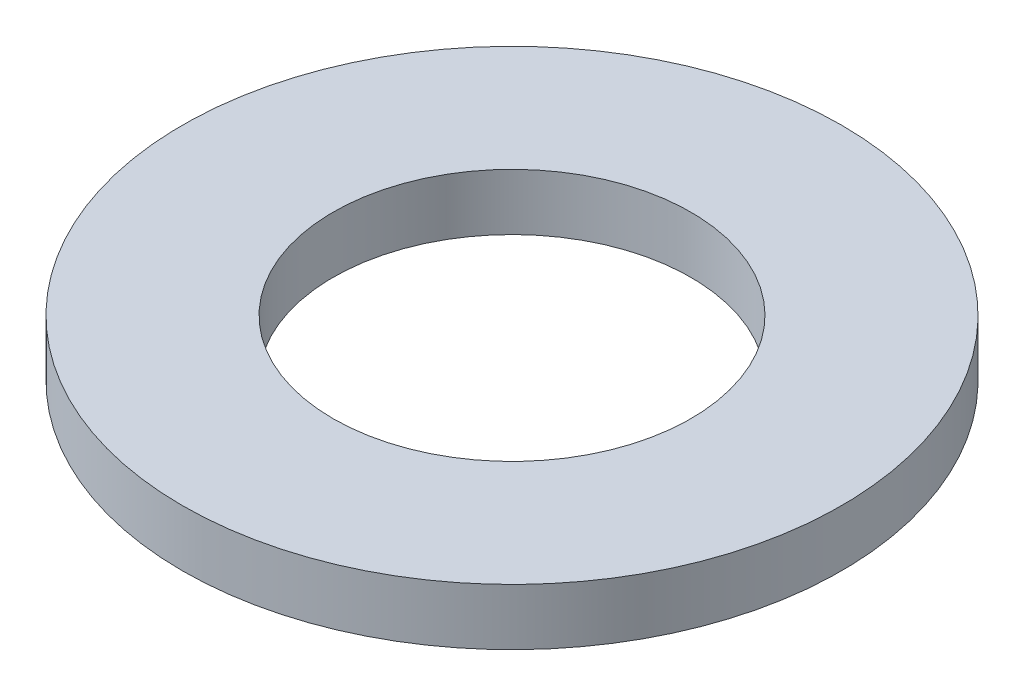
SolidWorks part; units mm, degrees
ref_plane "Front Plane" through (0, 0, 0) normal (0, 0, 1) x (1, 0, 0)
ref_plane "Top Plane" through (0, 0, 0) normal (0, 1, 0) x (1, 0, 0)
ref_plane "Right Plane" through (0, 0, 0) normal (1, 0, 0) x (0, 0, -1)
sketch "Sketch1" plane through (0, 0, 0) normal (0, 1, 0) x (1, 0, 0)
  circle A0 centre (0, 0) radius 87.5
  dimension "FLANGE_OD" = 175
extrude "Boss-Extrude1" add sketch "Sketch1" along normal blind 15
sketch "Sketch2" plane through (0, 0, 0) normal (0, 1, 0) x (1, 0, 0)
  circle A0 centre (0, 0) radius 47.5
  dimension "BORE_D" = 95
extrude "Cut-Extrude1" cut sketch "Sketch2" along normal through all
sketch "Sketch3" plane through (0, 15, 0) normal (0, 1, 0) x (1, 0, 0)
  circle A0 centre (0, 0) radius 29.6012 construction
  circle A1 centre (-29.6012, 0) radius 4.6311
  dimension "BOLT_D" = 9.2622
  dimension "BOLT_PCD" = 59.2024
extrude "Cut-Extrude2" cut sketch "Sketch3" against normal blind 12.4265 rebuild error yes
pattern_circular "CirPattern1" count 4 over 360 rebuild error yes
